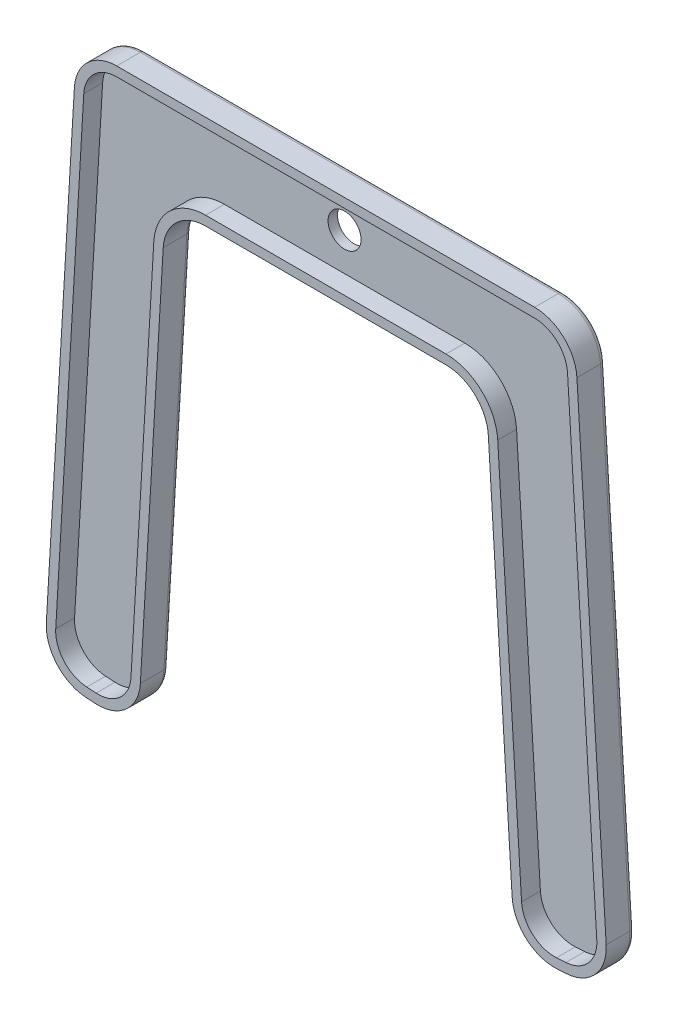
SolidWorks part; units mm, degrees
ref_plane "Plan de face" through (0, 0, 0) normal (0, 0, 1) x (1, 0, 0)
ref_plane "Plan de dessus" through (0, 0, 0) normal (0, 1, 0) x (1, 0, 0)
ref_plane "Plan de droite" through (0, 0, 0) normal (1, 0, 0) x (0, 0, -1)
sketch "Esquisse1" plane through (0, 0, 0) normal (0, 0, 1) x (1, 0, 0)
  line L0 (8.4869, 0) -> (59.5355, 0)
  line L1 (68.5186, -8.4486) -> (73.5753, -90.829)
  line L2 (-0.4976, -8.4723) -> (-5.3454, -91.0155)
  line L3 (0, 0) -> (74.1267, -99.8121) construction
  line L4 (68, 0) -> (-5.8731, -100) construction
  line L5 (-19.3574, 11.5277) -> (-25.311, -89.8429)
  line L6 (-10.3729, 20) -> (78.3455, 20)
  line L7 (87.3286, 11.5514) -> (93.5377, -89.6037)
  line L8 (-16.8542, -99.3551) -> (-14.8576, -99.4723)
  line L9 (85.106, -99.1382) -> (83.1098, -99.2607)
  line L10 (-18.8598, 20) -> (-25.8387, -98.8274) construction
  line L11 (0, 0) -> (-5.8731, -100) construction
  line L12 (86.81, 20) -> (94.0891, -98.5868) construction
  line L13 (68, 0) -> (74.1267, -99.8121) construction
  line L14 (-18.8598, 20) -> (86.81, 20) construction
  line L15 (0, 0) -> (68, 0) construction
  line L16 (-10.3729, 18) -> (78.3455, 18)
  line L17 (85.3323, 11.4289) -> (91.5415, -89.7262)
  line L18 (33.9863, 20) -> (34.0112, 0) construction
  line L19 (84.9835, -97.142) -> (82.9873, -97.2645)
  line L20 (70.5148, -8.3261) -> (75.5715, -90.7065)
  line L21 (8.4869, 2) -> (59.5355, 2)
  line L22 (-2.4941, -8.3551) -> (-7.342, -90.8982)
  line L23 (-16.7369, -97.3585) -> (-14.7403, -97.4758)
  line L24 (-17.3609, 11.4104) -> (-23.3144, -89.9601)
  arc A0 (-25.311, -89.8429) -> (-16.8542, -99.3551) centre (-16.3265, -90.3706) ccw
  arc A1 (-5.3454, -91.0155) -> (-14.8576, -99.4723) centre (-14.3299, -90.4878) cw
  arc A2 (93.5377, -89.6037) -> (85.106, -99.1382) centre (84.5546, -90.1551) cw
  arc A3 (73.5753, -90.829) -> (83.1098, -99.2607) centre (82.5584, -90.2776) ccw
  arc A4 (78.3455, 20) -> (87.3286, 11.5514) centre (78.3455, 11) cw
  arc A5 (59.5355, 0) -> (68.5186, -8.4486) centre (59.5355, -9) cw
  arc A6 (8.4869, 0) -> (-0.4976, -8.4723) centre (8.4869, -9) ccw
  arc A7 (-19.3574, 11.5277) -> (-10.3729, 20) centre (-10.3729, 11) cw
  circle A8 centre (33.9988, 10) radius 3.5
  arc A9 (78.3455, 18) -> (85.3323, 11.4289) centre (78.3455, 11) cw
  arc A10 (91.5415, -89.7262) -> (84.9835, -97.142) centre (84.5546, -90.1551) cw
  arc A11 (75.5715, -90.7065) -> (82.9873, -97.2645) centre (82.5584, -90.2776) ccw
  arc A12 (59.5355, 2) -> (70.5148, -8.3261) centre (59.5355, -9) cw
  arc A13 (8.4869, 2) -> (-2.4941, -8.3551) centre (8.4869, -9) ccw
  arc A14 (-7.342, -90.8982) -> (-14.7403, -97.4758) centre (-14.3299, -90.4878) cw
  arc A15 (-23.3144, -89.9601) -> (-16.7369, -97.3585) centre (-16.3265, -90.3706) ccw
  arc A16 (-17.3609, 11.4104) -> (-10.3729, 18) centre (-10.3729, 11) cw
  point P35 (33.9988, 10)
  point P38 (0, 0)
  dimension "D6" = 9
  dimension "D7" = 2
  dimension "D8" = 7
  dimension "D1" = 68
  dimension "D2" = 80
  dimension "D3" = 100
  dimension "D4" = 100
  dimension "D5" = 20
extrude "Boss.-Extru.1" add sketch "Esquisse1" along normal blind 2 contours L6 A4 L7 A2 L9 A3 L1 A5 L0 A6 L2 A1 L8 A0 L5 A7 | A8
extrude "Boss.-Extru.2" add sketch "Esquisse1<4>" along normal blind 4 from surface contours A7 L6 A4 L7 A2 L9 A3 L1 A5 L0 A6 L2 A1 L8 A0 L5 | A16 L16 A9 L17 A10 L19 A11 L20 A12 L21 A13 L22 A14 L23 A15 L24 starting at face at (34.0589, -44.5421, 2)
sketch "Esquisse1<4>" plane through (0, 0, 0) normal (0, 0, 1) x (1, 0, 0) same geometry as "Esquisse1"
fillet "Congé1" radius 1 16 edges at (-16.5475, 17.5479, 0) (33.9863, 20, 0) (84.5114, 17.556, 0) (90.4332, -39.0262, 0) (91.2965, -96.1172, 0) (84.1079, -99.1995, 0) (76.5963, -97.0196, 0) (71.0469, -49.6388, 0) (65.7014, -2.444, 0) (34.0112, 0, 0) (2.3123, -2.4521, 0) (-2.9215, -49.7439, 0) (-8.35, -97.2139, 0) (-15.8559, -99.4137, 0) (-23.0526, -96.3505, 0) (-22.3342, -39.1576, 0)
